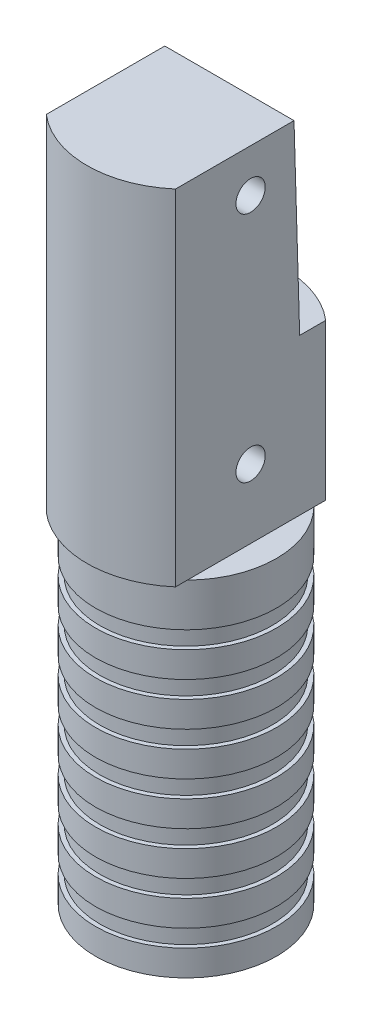
SolidWorks part; units mm, degrees
material "6061-T6 (SS)"
ref_plane "Front Plane" through (0, 0, 0) normal (0, 0, 1) x (1, 0, 0)
ref_plane "Top Plane" through (0, 0, 0) normal (0, 1, 0) x (1, 0, 0)
ref_plane "Right Plane" through (0, 0, 0) normal (1, 0, 0) x (0, 0, -1)
sketch "Sketch2" plane through (0, 0, 0) normal (0, 0, 1) x (1, 0, 0)
  line L0 (-10.5, 0) -> (10.5, 0)
  line L1 (10.5, 0) -> (10.5, -40)
  line L2 (10.5, -40) -> (-1, -40)
  line L4 (0, 0) -> (0, -40)
  line L6 (-10.5, -40) -> (-1, -40)
  line L7 (-10.5, 0) -> (-10.5, -40)
  point P4 (0, 0)
  dimension "D1" = 21
  dimension "D4" = 40
revolve "Revolve1" add sketch "Sketch2" angle 360 about L4 region at (-5.25, -20, 0)
sketch "Sketch3" plane through (0, 0, 0) normal (0, 0, 1) x (1, 0, 0)
  line L0 (-10.5, -40) -> (10.5, -40) construction
  line L1 (-10.5, -40) -> (10.5, -40)
  line L2 (10.5, -40) -> (10.5, -37)
  line L3 (10.5, -40) -> (10.5, 0) construction
  line L4 (10.5, -37) -> (10, -37)
  line L5 (10, -37) -> (10, -35)
  line L6 (10, -35) -> (10.5, -35)
  line L7 (10.5, -37) -> (10.5, -35)
  dimension "D1" = 2
  dimension "D2" = 0.5
  dimension "D3" = 3
revolve "Cut-Revolve1" cut sketch "Sketch3" angle 360 about L4
pattern_linear "LPattern1" count 7 spacing 5 along (0, 1, 0) of "Cut-Revolve1"
sketch "Sketch4" plane through (0, -40, 0) normal (0, -1, 0) x (1, 0, 0)
  point P0 (0, 0)
sketch "Sketch6" plane through (0, 0, 0) normal (0, 1, 0) x (1, 0, 0)
  line L0 (-7.5, 8.7178) -> (-7.5, -8.7178)
  line L2 (0, 0) -> (0, 11.5) construction
  line L3 (7.5, 8.7178) -> (7.5, -8.7178)
  line L4 (0, 0) -> (-7.5, 0) construction
  line L5 (-7.5, 1.5) -> (0, 1.5) construction
  arc A0 (7.5, 8.7178) -> (-7.5, 8.7178) centre (0, 0) ccw
  circle A1 centre (0, 0) radius 10.5 construction
  arc A2 (7.5, -8.7178) -> (-7.5, -8.7178) centre (0, 0) cw
  point P1 (0, 0)
  point P7 (-10.5, 0)
  dimension "D3" = 11.5
  dimension "D1" = 3
  dimension "D2" = 1.5
extrude "Boss-Extrude1" add sketch "Sketch6" along normal blind 40
hole_wizard "Ø15.0 (15) Diameter Hole1" positions "Sketch4" profile "Sketch5" hole size "Ø15.0" standard "ANSI Metric"
sketch "Sketch5" plane through (0, -40, 0) normal (1, 0, 0) x (0, 0, -1)
  line L0 (0, 0) -> (0, 34.5065)
  line L1 (0, 34.5065) -> (7.5, 30)
  line L2 (7.5, 30) -> (7.5, 0)
  line L5 (7.5, 0) -> (0, 0)
  line L10 (0, 34.5065) -> (-7.5, 30) construction
  line L11 (0, -6.35) -> (0, 107.95) construction
  dimension "Hole Dia." = 15
  dimension "Hole Depth" = 30
  dimension "Drill Angle" = 118
sketch "Sketch8" plane through (7.5, 0, 0) normal (1, 0, 0) x (0, 0, -1)
  line L2 (0, 8) -> (0, 35) construction
  line L3 (7.3485, 0) -> (-7.3485, 0) construction
  circle A0 centre (0, 8) radius 1.5 construction
  point P0 (0, 8)
  point P1 (0, 35)
  dimension "D1" = 3
  dimension "D2" = 8
  dimension "D3" = 27
hole_wizard "M3 Clearance Hole1" positions "Sketch8" profile "Sketch14" hole size "M3" standard "ANSI Metric" end condition through all
sketch "Sketch14" plane through (7.5, 8, 0) normal (0, 1, 0) x (0, 0, -1)
  line L0 (0, 0) -> (0, 18)
  line L1 (0, 18) -> (1.7, 18)
  line L2 (1.7, 18) -> (1.7, 0)
  line L5 (1.7, 0) -> (0, 0)
  line L11 (0, -6.35) -> (0, 107.95) construction
  dimension "Thru Hole Dia." = 3.4
  dimension "Thru Hole Depth" = 18
sketch "Sketch16" plane through (0, 0, 0) normal (1, 0, 0) x (0, 0, -1)
  line L0 (50.0175, 86.3497) -> (50.0175, 73.3497) construction
  line L1 (50.0175, -3.6503) -> (50.0175, 9.3497) construction
  line L2 (5.0377, 40) -> (5.6954, 18.0816)
  line L3 (5.6954, 18.0816) -> (11.5, 18.0816)
  line L4 (11.5, 40) -> (8.7178, 40) construction
  line L5 (11.5, 40) -> (8.7178, 40)
  line L6 (8.7178, 40) -> (5.0377, 40)
  line L8 (11.5, 18.0816) -> (11.5, 40)
  circle A0 centre (0, 8) radius 1.7 construction
  circle A1 centre (0, 35) radius 1.7 construction
  circle A2 centre (0, 8) radius 1.7
  circle A3 centre (0, 35) radius 1.7
  arc A4 (50.0175, -3.6503) -> (50.0175, 86.3497) centre (50.0175, 41.3497) cw construction
  arc A5 (50.0175, 73.3497) -> (50.0175, 9.3497) centre (50.0175, 41.3497) ccw construction
  dimension "D1" = 32
  dimension "D4" = 13
  dimension "D2" = 60.1162
  dimension "D3" = 50.4189
extrude "Cut-Extrude1" cut sketch "Sketch16" against normal through all both and the other way through all
